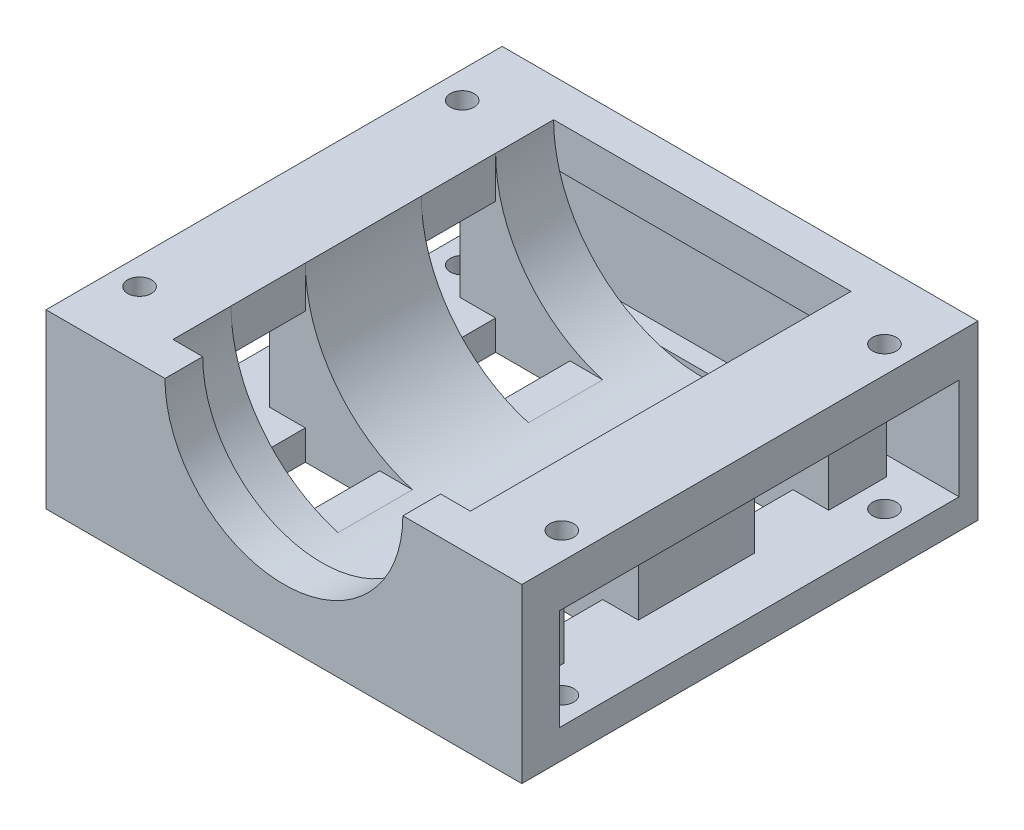
SolidWorks part; units mm, degrees
ref_plane "Front Plane" through (0, 0, 0) normal (0, 0, 1) x (1, 0, 0)
ref_plane "Top Plane" through (0, 0, 0) normal (0, 1, 0) x (1, 0, 0)
ref_plane "Right Plane" through (0, 0, 0) normal (1, 0, 0) x (0, 0, -1)
sketch "Sketch1" plane through (0, 0, 0) normal (0, 0, 1) x (1, 0, 0)
  line L0 (0, 0) -> (80, 0)
  line L1 (80, 0) -> (80, 5)
  line L2 (80, 5) -> (71, 5)
  line L3 (71, 5) -> (71, 22)
  line L4 (80, 29) -> (65, 29)
  line L7 (15, 29) -> (0, 29)
  line L8 (9, 22) -> (9, 5)
  line L9 (9, 5) -> (0, 5)
  line L10 (0, 5) -> (0, 0)
  line L12 (0, 29) -> (0, 22)
  line L13 (0, 22) -> (9, 22)
  line L14 (80, 29) -> (80, 22)
  line L15 (80, 22) -> (71, 22)
  arc A0 (15, 29) -> (65, 29) centre (40, 29) ccw
  dimension "D1" = 50
  dimension "D2" = 9
  dimension "D3" = 5
  dimension "D4" = 7
  dimension "D5" = 15
  dimension "D6" = 17
extrude "Boss-Extrude1" add sketch "Sketch1" along normal blind 64
ref_plane "Plane1" through (0, 0, 64) normal (0, 0, 1) x (1, 0, 0)
sketch "Sketch2" plane through (0, 0, 64) normal (0, 0, 1) x (1, 0, 0)
  line L0 (60, 29) -> (80, 29)
  line L1 (0, 0) -> (80, 0)
  line L2 (0, 0) -> (0, 29)
  line L3 (0, 29) -> (20, 29)
  line L4 (80, 0) -> (80, 29)
  line L5 (40, 0) -> (40, 29) construction
  arc A0 (20, 29) -> (60, 29) centre (40, 29) ccw
  dimension "D1" = 40
extrude "Boss-Extrude2" add sketch "Sketch2" along normal blind 6.35
ref_plane "Plane2" through (0, 29, 0) normal (0, 1, 0) x (1, 0, 0)
sketch "Sketch3" plane through (0, 29, 0) normal (0, 1, 0) x (1, 0, 0)
  line L0 (15, -64) -> (15, 0) construction
  line L1 (15, -9.75) -> (27.5, -9.75)
  line L2 (15, -9.75) -> (15, -22.25)
  line L3 (15, -22.25) -> (27.5, -22.25)
  line L4 (27.5, -9.75) -> (27.5, -22.25)
  line L5 (40, 0) -> (40, -64) construction
  line L6 (65, 0) -> (15, 0) construction
  line L7 (-15.95, -64) -> (15.95, -64) construction
  line L8 (40, -32) -> (15, -32) construction
  line L9 (15, 0) -> (65, -64) construction
  line L10 (65, 0) -> (15, -64) construction
  line L11 (15, -32) -> (40, 0) construction
  line L12 (27.5, -16) -> (15, -16) construction
  line L13 (65, -64) -> (65, 0) construction
  line L14 (65, -64) -> (60, -64) construction
  line L15 (65, -22.25) -> (52.5, -22.25)
  line L16 (52.5, -9.75) -> (52.5, -22.25)
  line L17 (65, -9.75) -> (52.5, -9.75)
  line L18 (65, -9.75) -> (65, -22.25)
  line L19 (15, -41.75) -> (27.5, -41.75)
  line L20 (27.5, -54.25) -> (27.5, -41.75)
  line L21 (15, -54.25) -> (27.5, -54.25)
  line L22 (15, -54.25) -> (15, -41.75)
  line L23 (65, -54.25) -> (65, -41.75)
  line L24 (65, -54.25) -> (52.5, -54.25)
  line L25 (52.5, -54.25) -> (52.5, -41.75)
  line L26 (65, -41.75) -> (52.5, -41.75)
  point P23 (15, -16)
extrude "Cut-Extrude1" cut sketch "Sketch3" against normal up to surface (29 mm away) up to face at (40, 0, 35.175)
ref_plane "Plane3" through (15, 0, 0) normal (1, 0, 0) x (0, 0, -1)
sketch "Sketch5" plane through (15, 0, 0) normal (1, 0, 0) x (0, 0, -1)
  line L0 (-54.25, 0) -> (-54.25, 29) construction
  line L1 (-54.25, 22) -> (-41.75, 22)
  line L2 (-54.25, 22) -> (-54.25, 5)
  line L3 (-54.25, 5) -> (-41.75, 5)
  line L4 (-41.75, 22) -> (-41.75, 5)
  line L5 (-41.75, 0) -> (-41.75, 29) construction
  line L8 (-54.25, 22) -> (-54.25, 29) construction
  line L9 (-54.25, 0) -> (-54.25, 5) construction
  line L16 (-22.25, 22) -> (-9.75, 22)
  line L17 (-22.25, 22) -> (-22.25, 5)
  line L18 (-22.25, 5) -> (-9.75, 5)
  line L19 (-9.75, 22) -> (-9.75, 5)
  line L20 (-22.25, 0) -> (-22.25, 7.3494) construction
  line L21 (-9.75, 0) -> (-9.75, 29) construction
  dimension "D1" = 7
  dimension "D2" = 5
extrude "Cut-Extrude2" cut sketch "Sketch5" against normal up to surface and the other way up to surface up to face at (9, 13.5, 32) other way up to face at (71, 13.5, 32)
ref_plane "Plane4" through (0, 0, 0) normal (0, -1, 0) x (-1, 0, 0)
sketch "Sketch6" plane through (0, 0, 0) normal (0, -1, 0) x (-1, 0, 0)
  line L0 (-4.8728, -32) -> (0, -32) construction
  line L1 (-15, 0) -> (-15, -70.35) construction
  line L2 (-15, 15.95) -> (-15, -15.95) construction
  line L3 (0, -70.35) -> (-80, -70.35) construction
  line L4 (-15, -54.25) -> (0, -64) construction
  line L5 (-27.5, -54.25) -> (-15, -54.25) construction
  line L7 (0, -70.35) -> (0, 0) construction
  line L9 (0, 0) -> (-80, 0) construction
  line L10 (-40, -70.35) -> (-40, 0) construction
  line L11 (0, -64) -> (-15, -64) construction
  line L12 (-15.95, -64) -> (15.95, -64) construction
  line L13 (0, -64) -> (-15, 0) construction
  line L14 (0, -64) -> (-8.9998, -64) construction
  line L15 (-8.9998, -64) -> (-8.9998, -54.25) construction
  line L16 (-8.9998, -54.25) -> (0, -54.25) construction
  line L17 (0, -54.25) -> (-8.9998, -64) construction
  line L18 (0, -64) -> (-8.9998, -54.25) construction
  circle A0 centre (-4.4999, -59.125) radius 2
  circle A1 centre (-4.4999, -4.875) radius 2
  circle A2 centre (-75.5001, -4.875) radius 2
  circle A3 centre (-75.5001, -59.125) radius 2
  point P13 (-4.4999, -59.125)
  dimension "D1" = 4
extrude "Cut-Extrude3" cut sketch "Sketch6" against normal up to surface (29 mm away) up to face at (67, 29, 39.67)
ref_plane "Plane5" through (0, 0, 0) normal (0, 0, -1) x (-1, 0, 0)
sketch "Sketch7" plane through (0, 0, 0) normal (0, 0, -1) x (-1, 0, 0)
  line L1 (-80, 0) -> (0, 0)
  line L2 (-80, 0) -> (-80, 29)
  line L3 (-80, 29) -> (0, 29)
  line L4 (0, 0) -> (0, 29)
extrude "Boss-Extrude3" add sketch "Sketch7" along normal blind 6.35
ref_plane "Plane6" through (80, 0, 0) normal (1, 0, 0) x (0, 0, -1)
sketch "Sketch8" plane through (80, 0, 0) normal (1, 0, 0) x (0, 0, -1)
  line L0 (0, 5) -> (6.35, 5) construction
  line L1 (0, 22) -> (3.175, 22)
  line L2 (0, 22) -> (0, 5)
  line L3 (0, 5) -> (3.175, 5)
  line L4 (3.175, 22) -> (3.175, 5)
  line L5 (6.35, 29) -> (6.35, 0) construction
  line L6 (0, 22) -> (6.35, 5) construction
  line L8 (0, 5) -> (6.35, 22) construction
  point P2 (3.175, 13.5)
  point P12 (3.175, 13.5)
extrude "Cut-Extrude4" cut sketch "Sketch8" against normal up to surface (80 mm away) up to face at (0, 14.5, 32)
